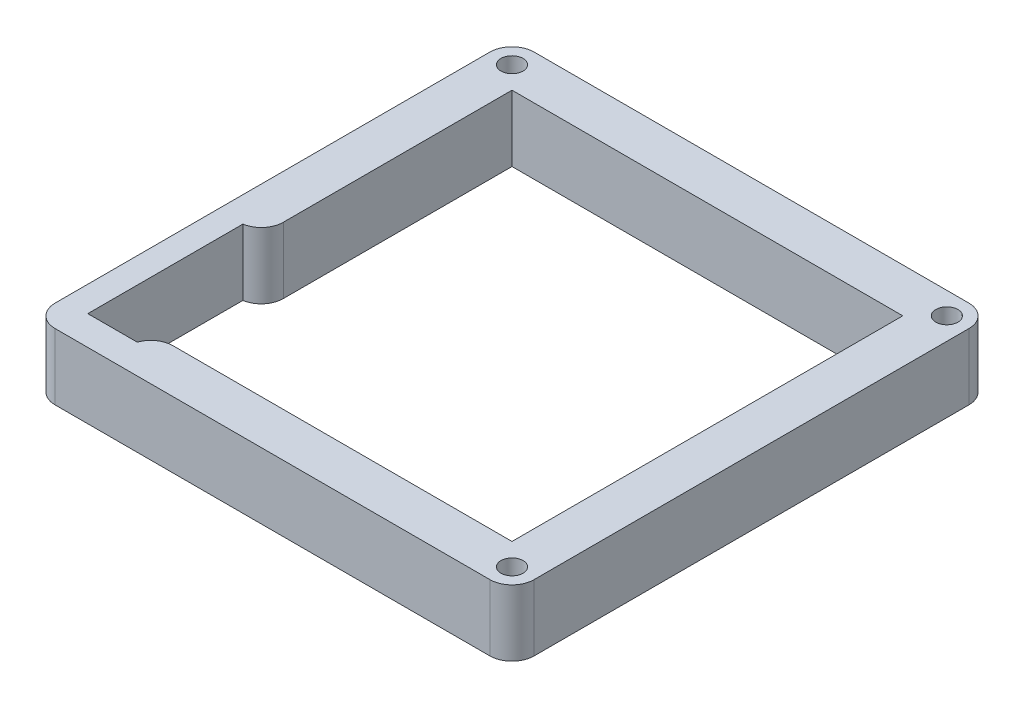
SolidWorks part; units mm, degrees
ref_plane "Front Plane" through (0, 0, 0) normal (0, 0, 1) x (1, 0, 0)
ref_plane "Top Plane" through (0, 0, 0) normal (0, 1, 0) x (1, 0, 0)
ref_plane "Right Plane" through (0, 0, 0) normal (1, 0, 0) x (0, 0, -1)
sketch "Sketch1" plane through (0, 0, 0) normal (0, 1, 0) x (1, 0, 0)
  line L1 (-62.6306, 62.6306) -> (62.6306, 62.6306) construction
  line L2 (-62.6306, 62.6306) -> (-62.6306, -62.6306) construction
  line L3 (-62.6306, -62.6306) -> (62.6306, -62.6306) construction
  line L4 (62.6306, 62.6306) -> (62.6306, -62.6306) construction
  line L5 (-62.6306, 62.6306) -> (62.6306, -62.6306) construction
  line L6 (-62.6306, -62.6306) -> (62.6306, 62.6306) construction
  circle A0 centre (-62.6306, 62.6306) radius 3.175
  circle A1 centre (62.6306, 62.6306) radius 3.175
  circle A2 centre (62.6306, -62.6306) radius 3.175
  point P0 (0, 0)
  line B0 (68.9806, 68.9806) -> (-68.9806, 68.9806)
  line B1 (68.9806, 68.9806) -> (68.9806, -68.9806)
  line B2 (68.9806, -68.9806) -> (-68.9806, -68.9806)
  line B3 (-68.9806, 68.9806) -> (-68.9806, -68.9806)
  line B4 (68.9806, 68.9806) -> (-68.9806, -68.9806) construction
  line B5 (68.9806, -68.9806) -> (-68.9806, 68.9806) construction
  line B6 (-61.6371, -15.8746) -> (-47.3877, -15.8746)
  line B7 (-61.6371, -15.8746) -> (-61.6371, -60.546)
  line B8 (-61.6371, -60.546) -> (-47.3877, -60.546)
  line B9 (-47.3877, -15.8746) -> (-47.3877, -60.546)
  line B10 (-56.2806, 56.2806) -> (56.2806, 56.2806)
  line B11 (-56.2806, 56.2806) -> (-56.2806, -56.2806)
  line B12 (-56.2806, -56.2806) -> (56.2806, -56.2806)
  line B13 (56.2806, 56.2806) -> (56.2806, -56.2806)
  line B14 (-56.2806, 56.2806) -> (56.2806, -56.2806) construction
  line B15 (-56.2806, -56.2806) -> (56.2806, 56.2806) construction
  dimension "D2" = 6.35
  dimension "D1" = 6.35
sketch_block_instance "Block-Electronics Siding-1"
sketch_block "Block-Electronics Siding" parameters "D1"=12.7, "D2"=12.7
extrude "Boss-Extrude1" add sketch "Sketch1" along normal blind 19.05 contours B0 B3 B2 B1 A0 A1 A2 B10 B13 B12 B9 B8 B7 B6 B11 region at (67.0295, 0, 0)
fillet "Fillet1" radius 6.35 4 edges at (68.9806, 9.525, -68.9806) (68.9806, 9.525, 68.9806) (-68.9806, 9.525, 68.9806) (-68.9806, 9.525, -68.9806)
fillet "Fillet2" radius 6.35 2 edges at (-56.2806, 9.525, 15.8746) (-47.3877, 9.525, 56.2806)
